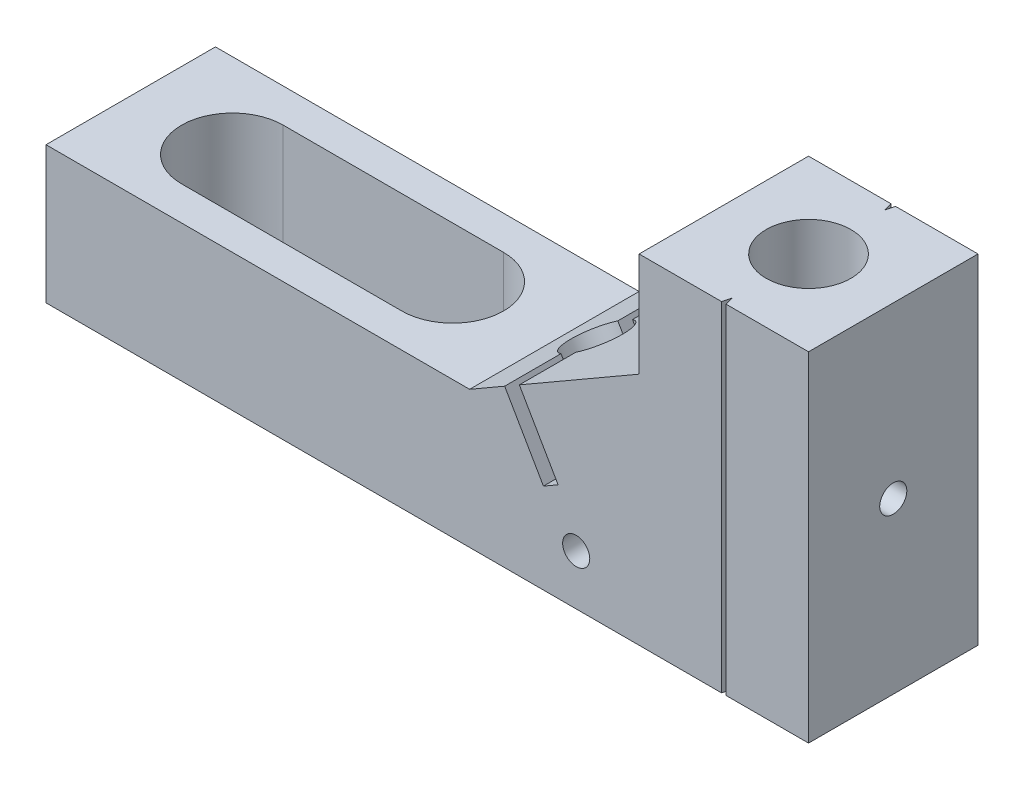
SolidWorks part; units mm, degrees
ref_plane "Front Plane" through (0, 0, 0) normal (0, 0, 1) x (1, 0, 0)
ref_plane "Top Plane" through (0, 0, 0) normal (0, 1, 0) x (1, 0, 0)
ref_plane "Right Plane" through (0, 0, 0) normal (1, 0, 0) x (0, 0, -1)
sketch "Sketch1" plane through (0, 0, 0) normal (0, 1, 0) x (1, 0, 0)
  line L1 (-13.6389, 9.0278) -> (6.3611, 9.0278)
  line L2 (-13.6389, 9.0278) -> (-13.6389, -0.9722)
  line L3 (-13.6389, -0.9722) -> (6.3611, -0.9722)
  line L4 (6.3611, 9.0278) -> (6.3611, -0.9722)
  dimension "D1" = 20
  dimension "D2" = 10
extrude "Boss-Extrude1" add sketch "Sketch1" along normal blind 20
sketch "Sketch2" plane through (0, 20, 0) normal (0, 1, 0) x (1, 0, 0)
  line L0 (-13.6389, 4.0278) -> (6.3611, 4.0278) construction
  line L1 (-13.6389, 9.0278) -> (-13.6389, -0.9722) construction
  line L2 (6.3611, -0.9722) -> (6.3611, 9.0278) construction
  line L3 (1.4951, -0.9722) -> (1.3611, -0.4722)
  line L4 (-13.6389, -0.9722) -> (6.3611, -0.9722) construction
  line L5 (1.3611, -0.4722) -> (1.2271, -0.9722)
  line L6 (1.4951, -0.9722) -> (1.2271, -0.9722)
  line L7 (1.3611, 8.5278) -> (1.2271, 9.0278)
  line L8 (1.4951, 9.0278) -> (1.3611, 8.5278)
  line L9 (1.4951, 9.0278) -> (1.2271, 9.0278)
  circle A0 centre (1.3611, 4.0278) radius 2.5
  point P15 (-3.6389, -0.9722)
  point P17 (0, 0)
  point P18 (10.3065, -0.9722)
  point P19 (0, 0)
  dimension "D1" = 5
  dimension "D2" = 5
  dimension "D3" = 30
  dimension "D4" = 0.5
extrude "Cut-Extrude1" cut sketch "Sketch2" against normal through all
sketch "Sketch3" plane through (0, 0, 0.9722) normal (0, 0, 1) x (1, 0, 0)
  line L0 (-13.6389, 20) -> (-3.6389, 20)
  line L1 (-13.6389, 20) -> (1.2271, 20) construction
  line L2 (-3.6389, 13.8564) -> (-10.7059, 9.7763)
  line L3 (-13.6389, 20) -> (-13.6389, 0) construction
  line L4 (-13.6389, 8.0829) -> (-13.6389, 20)
  line L5 (-3.6389, 13.8564) -> (-3.6389, 20)
  line L6 (-13.6389, 0) -> (1.2271, 0) construction
  line L7 (-11.1389, 9.5263) -> (-5.6389, 0) construction
  line L8 (6.3611, 20) -> (6.3611, 0) construction
  line L10 (-10.7059, 9.7763) -> (-8.4174, 5.8125)
  line L11 (-11.5719, 9.2763) -> (-9.2834, 5.3125)
  line L12 (-8.4174, 5.8125) -> (-9.2834, 5.3125)
  line L13 (-11.5719, 9.2763) -> (-13.6389, 8.0829)
  point P1 (-8.8504, 5.5625)
  point P17 (-8.3889, 4.7631)
  point P22 (1.6782, 12.5071)
  dimension "D1" = 30
  dimension "D2" = 11
  dimension "D3" = 12
  dimension "D4" = 10
  dimension "D5" = 1
  dimension "D6" = 4.577
extrude "Cut-Extrude2" cut sketch "Sketch3" against normal through all
sketch "Sketch5" plane through (-6.9097, 11.968, 0) normal (-0.5, 0.866, 0) x (0.866, 0.5, 0)
  line L0 (-4.3834, 9.0278) -> (-4.3834, -0.9722) construction
  line L1 (-4.3834, 4.0278) -> (-5.3834, 4.0278) construction
  line L2 (-5.3834, 9.0278) -> (-5.3834, -0.9722) construction
  circle A0 centre (-4.8834, 4.0278) radius 1.75
  point P5 (-4.3834, 4.0278)
  point P9 (0, 0)
  dimension "D1" = 3.5
extrude "Cut-Extrude5" cut sketch "Sketch5" against normal through all
sketch "Sketch6" plane through (6.3611, 0, 0) normal (1, 0, 0) x (0, 0, -1)
  line L0 (9.0278, 20) -> (9.0278, 0) construction
  line L1 (-0.9722, 20) -> (9.0278, 20) construction
  point P0 (4.0278, 10)
  point P1 (0, 0)
  point P4 (9.0278, 10)
  point P5 (0, 0)
  point P8 (4.0278, 20)
hole_wizard "M2x0.4 Tapped Hole1" positions "Sketch7" profile "Sketch8" tap size "M2x0.4" standard "BSI"
sketch "Sketch7" plane through (6.3611, 0, 0) normal (1, 0, 0) x (0, 0, -1)
  point P0 (4.0278, 10)
sketch "Sketch8" plane through (6.3611, 10, -4.0278) normal (0, 1, 0) x (0, 0, -1)
  line L0 (0, 0) -> (0, 6.4807)
  line L1 (0, 6.4807) -> (0.8, 6)
  line L2 (0.8, 6) -> (0.8, 0)
  line L5 (0.8, 0) -> (0, 0)
  line L10 (0, 6.4807) -> (-0.8, 6) construction
  line L11 (0, -6.35) -> (0, 107.95) construction
  dimension "Tap Drill Dia." = 1.6
  dimension "Tap Drill Depth" = 6
  dimension "Drill Angle" = 118
cosmetic thread "Hole Thread1" parameters "D1"=4, "D2"=2
hole_wizard "M2x0.4 Tapped Hole2" positions "Sketch9" profile "Sketch10" tap size "M2x0.4" standard "BSI"
sketch "Sketch9" plane through (0, 0, 0.9722) normal (0, 0, 1) x (1, 0, 0)
  line L0 (-9.2834, 5.3125) -> (-8.4174, 5.8125) construction
  line L1 (-7.3504, 2.9644) -> (-8.8504, 5.5625) construction
  point P0 (-7.3504, 2.9644)
  dimension "D1" = 3
sketch "Sketch10" plane through (-7.3504, 2.9644, 0.9722) normal (1, 0, 0) x (0, -1, 0)
  line L0 (0, 0) -> (0, 6.4807)
  line L1 (0, 6.4807) -> (0.8, 6)
  line L2 (0.8, 6) -> (0.8, 0)
  line L5 (0.8, 0) -> (0, 0)
  line L10 (0, 6.4807) -> (-0.8, 6) construction
  line L11 (0, -6.35) -> (0, 107.95) construction
  dimension "Tap Drill Dia." = 1.6
  dimension "Tap Drill Depth" = 6
  dimension "Drill Angle" = 118
cosmetic thread "Hole Thread2" parameters "D1"=4, "D2"=2
sketch "Sketch14" plane through (-13.6389, 0, 0) normal (-1, 0, 0) x (0, 0, 1)
  line L4 (0.9722, 0) -> (0.9722, 8.0829)
  line L5 (0.9722, 8.0829) -> (-9.0278, 8.0829)
  line L6 (-9.0278, 8.0829) -> (-9.0278, 0)
  line L7 (-9.0278, 0) -> (0.9722, 0)
  line L8 (0.9722, 0) -> (0.9722, 8.0829)
  line L9 (0.9722, 8.0829) -> (-9.0278, 8.0829)
  line L10 (-9.0278, 8.0829) -> (-9.0278, 0)
  line L11 (-9.0278, 0) -> (0.9722, 0)
  dimension "D1" = 0
extrude "Boss-Extrude3" add sketch "Sketch14" along normal blind 25
sketch "Sketch15" plane through (0, 8.0829, 0) normal (0, 1, 0) x (1, 0, 0)
  line L0 (-13.6389, 9.0278) -> (-13.6389, -0.9722) construction
  line L1 (-38.6389, -0.9722) -> (-38.6389, 9.0278) construction
  line L2 (-32.6389, 4.0278) -> (-19.6389, 4.0278) construction
  line L3 (-38.6389, -0.9722) -> (-13.6389, -0.9722) construction
  line L4 (-19.6389, 1.0278) -> (-32.6389, 1.0278)
  line L5 (-32.6389, 7.0278) -> (-19.6389, 7.0278)
  line L6 (-38.6389, 9.0278) -> (-13.6389, 9.0278) construction
  arc A0 (-19.6389, 1.0278) -> (-19.6389, 7.0278) centre (-19.6389, 4.0278) ccw
  arc A1 (-32.6389, 7.0278) -> (-32.6389, 1.0278) centre (-32.6389, 4.0278) ccw
  point P1 (-17.1389, 1.0278)
  point P2 (-26.1389, 4.0278)
  point P5 (-13.6389, 4.0278)
  point P7 (0, 0)
  point P11 (-38.6389, 4.0278)
  point P13 (-26.1389, -0.9722)
  dimension "D1" = 6
  dimension "D2" = 6
  dimension "D3" = 13
extrude "Cut-Extrude7" cut sketch "Sketch15" against normal up to next
